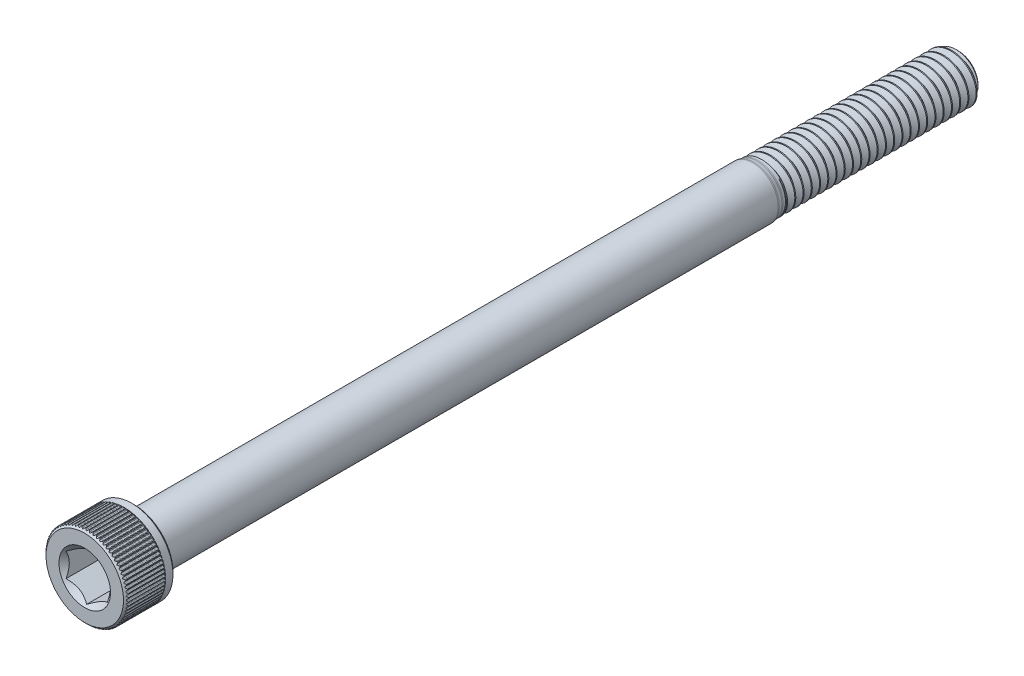
SolidWorks part; units mm, degrees
ref_plane "Front Plane" through (0, 0, 0) normal (0, 0, 1) x (1, 0, 0)
ref_plane "Top Plane" through (0, 0, 0) normal (0, 1, 0) x (1, 0, 0)
ref_plane "Right Plane" through (0, 0, 0) normal (1, 0, 0) x (0, 0, -1)
sketch "Sketch1" plane through (0, 0, 0) normal (1, 0, 0) x (0, 0, -1)
  line L0 (-53, 0) -> (53, 0) construction
  line L1 (53, 0) -> (53, 2.3505) construction
  line L2 (53, 2.3505) -> (52.3505, 3) construction
  line L3 (52.3505, 3) -> (52.25, 3) construction
  line L4 (52.25, 3) -> (-47, 3) construction
  line L5 (-47, 3) -> (-47, 5) construction
  line L6 (-47, 5) -> (-53, 5) construction
  line L7 (-53, 5) -> (-53, 0) construction
  line L8 (53, 2.3505) -> (53, 3) construction
  line L9 (52.9375, 3.1083) -> (53.4375, 2.2422) construction
  line L10 (53.4375, 2.2422) -> (53.9375, 3.1083) construction
  line L11 (53.9375, 3.1083) -> (52.9375, 3.1083) construction
  line L12 (53.4375, 3.1083) -> (53.4375, 3) construction
  line L13 (53.4375, 2.2422) -> (53.4375, 2.3505) construction
  line L14 (53.375, 2.3505) -> (53.5, 2.3505) construction
  line L15 (53, 3) -> (53.875, 3) construction
  line L16 (52.9688, 3.0541) -> (53.9062, 3.0541) construction
  line L17 (53, 0) -> (53, -3) construction
  line L18 (-47.3, 5) -> (-47, 4.7) construction
  line L19 (-52.7, 5) -> (-53, 4.7) construction
  line L20 (-47, 3) -> (-47, 0) construction
  line L21 (-47, 1.5) -> (-13.6667, 1.5) construction
  line L22 (-13.6667, 1.5) -> (19.6667, 1.5) construction
  line L23 (19.6667, 1.5) -> (53, 1.5) construction
  line L24 (-13.6667, 1.5) -> (-13.6667, 3) construction
  line L25 (-13.6667, 3) -> (-13.6667, 5) construction
  line L26 (19.6667, 1.5) -> (19.6667, 5) construction
  point P0 (-53, 2.5)
  point P3 (50.5, 3)
  point P4 (0, 0)
  point P18 (19.6667, 3)
  point P22 (53.4375, 2.3505)
  point P24 (52.25, 3)
  point P25 (53.4375, 3)
  point P28 (53.4375, 3.0541)
  point P29 (50.5, -3)
  point P30 (-13.6667, 3)
  point P31 (-50, 5)
  point P37 (-48.05, 5)
  point P38 (-52.55, 5)
  point P45 (-13.6667, 1.5)
  point P46 (19.6667, 1.5)
  point P49 (29, 3)
  dimension "D1" = 45
  dimension "D2" = 0.125
  dimension "D7" = 0.3
  dimension "D8" = 0.3
  dimension "D9" = 0.3
  dimension "D10" = 0.15
  dimension "D11" = 0.75
  dimension "Drive Size" = 5
  dimension "Head Diameter" = 10
  dimension "Head Height" = 6
  dimension "Thread Pitch" = 1
  dimension "Thread Size" = 6
  dimension "Length" = 100
  dimension "D12" = 0.75
  dimension "D4" = 2.5
  dimension "Minimum Thread Length" = 24
  dimension "D3" = 76
sketch "Sketch2" plane through (0, 0, 0) normal (1, 0, 0) x (0, 0, -1)
  line L0 (-53, 0) -> (-53, 4.7)
  line L1 (-52.7, 5) -> (-47.3, 5)
  line L2 (-47, 4.7) -> (-47, 3.4083)
  line L4 (52.3505, 3) -> (53, 2.3505)
  line L5 (53, 2.3505) -> (53, 0)
  line L6 (-47, 5) -> (-53, 5) construction
  line L7 (53, 0) -> (-53, 0)
  line L8 (-52.7, 5) -> (-53, 4.7) construction
  line L10 (-52.7, 5) -> (-53, 4.7)
  line L14 (-47.3, 5) -> (-47, 4.7) construction
  line L16 (-47.3, 5) -> (-47, 4.7)
  line L17 (-47, 3) -> (-47, 5) construction
  line L18 (-46.7, 3.1083) -> (28.0069, 3.1083)
  line L19 (28.6989, 3) -> (52.3505, 3)
  line L20 (52.25, 3) -> (-47, 3) construction
  line L21 (28.1532, 3.0938) -> (28.5526, 3.0144)
  line L22 (53.9375, 3.1083) -> (52.9375, 3.1083) construction
  arc A1 (-47, 3.4083) -> (-46.7, 3.1083) centre (-46.7, 3.4083) ccw
  arc A2 (28.0069, 3.1083) -> (28.1532, 3.0938) centre (28.0069, 2.3583) cw
  arc A3 (28.5526, 3.0144) -> (28.6989, 3) centre (28.6989, 3.75) ccw
  point P39 (28.625, 3)
  dimension "D3" = 0.3
  dimension "D6" = 0.75
  dimension "D4" = 11.25
  dimension "D5" = 0.375
revolve "Revolve1" add sketch "Sketch2" angle 360 about L7
sketch "Sketch3" plane through (0, 0, 53) normal (0, 0, 1) x (1, 0, 0)
  line L1 (2.5, -1.4434) -> (2.5, 1.4434)
  line L2 (2.5, 1.4434) -> (0, 2.8868)
  line L3 (0, 2.8868) -> (-2.5, 1.4434)
  line L4 (-2.5, 1.4434) -> (-2.5, -1.4434)
  line L5 (-2.5, -1.4434) -> (0, -2.8868)
  line L6 (0, -2.8868) -> (2.5, -1.4434)
  circle A0 centre (0, 0) radius 2.5 construction
  circle A1 centre (0, 0) radius 5 construction
  circle A2 centre (0, 0) radius 5 construction
  circle A3 centre (0, 0) radius 2.8868 construction
extrude "Cut-Extrude1" cut sketch "Sketch3" against normal offset from surface (5 mm away) 1 up to face at (0, 4.7, 47)
sketch "Sketch4" plane through (0, 0, 53) normal (0, 0, 1) x (1, 0, 0)
  circle A0 centre (0, 0) radius 3.125
  dimension "D1" = 6.25
extrude "Cut-Extrude2" cut sketch "Sketch4" against normal up to vertex (3 mm away) draft 45 up to point (0, 5, 50)
sketch "Sketch11" plane through (0, 0, 0) normal (1, 0, 0) x (0, 0, -1)
  line L0 (-53, 0) -> (53, 0) construction
  line L1 (-53, 0) -> (53, 0) construction
  line L2 (-40.35, 0) -> (-40.35, 3) construction
  line L3 (52.25, 3) -> (-47, 3) construction
  line L4 (21.3569, 0) -> (21.3569, 3) construction
  point P2 (-40.35, 0)
  point P3 (21.3569, 0)
  dimension "D1" = 6.65
  dimension "D2" = 6.65
sketch "Sketch6" plane through (0, 0, -53) normal (0, 0, -1) x (-1, 0, 0)
  circle A0 centre (0, 0) radius 3
curve "Helix/Spiral1" pitch 1 height 25 radius 3 centre (0, 0, -53) axis (0, 0, 1) start towards (0, 1, 0)
sketch "Sketch10" plane through (0, 0, 0) normal (1, 0, 0) x (0, 0, -1)
  line L0 (29, -3) -> (29, 3)
  line L2 (-53, 0) -> (53, 0) construction
  point P3 (29, 0)
split "Split1" trim tools "Sketch10" bodies to split 106 resulting bodies 114 115
sketch "Sketch7" plane through (0, 0, 0) normal (1, 0, 0) x (0, 0, -1)
  line L0 (52.9688, 3.0541) -> (53.9062, 3.0541)
  line L1 (53.9062, 3.0541) -> (53.5, 2.3505)
  line L2 (53.5, 2.3505) -> (53.375, 2.3505)
  line L3 (53.375, 2.3505) -> (52.9688, 3.0541)
sweep "Cut-Sweep1" cut profiles "Sketch7" path "Helix/Spiral1" align with end faces yes
sketch "Sketch8" plane through (0, 0, 0) normal (1, 0, 0) x (0, 0, -1)
  line L0 (-47, 0) -> (-47, 3)
  line L2 (-47, 3) -> (29, 3)
  line L4 (29, 3) -> (30.7321, 0)
  line L5 (30.7321, 0) -> (-47, 0)
  line L6 (52.25, 3) -> (-47, 3) construction
  line L7 (-53, 0) -> (53, 0) construction
  dimension "D1" = 60
  dimension "D2" = 24
revolve "Revolve2" add sketch "Sketch8" angle 360 about L5
ref_plane "Plane1" through (0, 0, 53) normal (0, 0, 1) x (1, 0, 0)
sketch "Sketch12" plane through (0, 0, 53) normal (0, 0, 1) x (1, 0, 0)
  line L0 (0, 0) -> (0.1745, 4.997) construction
  line L1 (0, 0) -> (-0.1745, 4.997) construction
  line L2 (0, 5.125) -> (0, 4.875) construction
  line L3 (-0.3025, 5.125) -> (-0.0897, 4.9122)
  line L4 (0.0897, 4.9122) -> (0.3025, 5.125)
  line L5 (0.3025, 5.125) -> (-0.3025, 5.125)
  circle A0 centre (0, 0) radius 5 construction
  arc A1 (-0.0897, 4.9122) -> (0.0897, 4.9122) centre (0, 5.0019) ccw
  point P12 (0, 5)
  point P14 (0, 5.125)
  dimension "D2" = 0.125
  dimension "D1" = 4
extrude "Cut-Extrude3" cut sketch "Sketch12" against normal blind 4.8
pattern_circular "CirPattern1" count 72 over 360 about axis through (0, 0, 53) along (0, 0, -1) of "Cut-Extrude3"
equation "\"D2@Sketch1\" = \"Thread Pitch@Sketch1\" / 8"
equation "\"D4@Helix/Spiral1\" = \"Thread Pitch@Sketch1\""
equation "\"D7@Sketch1\" = \"Head Height@Sketch1\" * .05"
equation "\"D8@Sketch1\"=\"D7@Sketch1\""
equation "\"D9@Sketch1\"=\"D7@Sketch1\""
equation "\"D10@Sketch1\"=\"D7@Sketch1\"/2"
equation "\"D11@Sketch1\"=\"D10@Sketch1\"*5"
equation "\"D4@Sketch1\"=\"Thread Pitch@Sketch1\"*2.5"
equation "\"D12@Sketch1\"=\"Thread Pitch@Sketch1\"*.75"
equation "\"D3@Helix/Spiral1\"=\"Minimum Thread Length@Sketch1\"+\"Thread Pitch@Sketch1\""
equation "\"D2@Sketch8\"=\"Minimum Thread Length@Sketch1\""
equation "\"D3@Sketch2\"=\"Thread Size@Sketch1\"*0.05"
equation "\"D5@Sketch2\"=\"D12@Sketch1\"*0.5"
equation "\"D6@Sketch2\"=\"Thread Size@Sketch1\"*0.125"
equation "\"D1@Sketch11\"=(\"Length@Sketch1\"-\"Minimum Thread Length@Sketch1\")*0.0875"
equation "\"D2@Sketch11\"=\"D1@Sketch11\""
equation "\"D1@Sketch4\"=\"Drive Size@Sketch1\"*1.25"
equation "\"D2@Sketch12\"=\"Head Diameter@Sketch1\"*.0125"
equation "\"D1@Cut-Extrude3\"=\"Head Height@Sketch1\"*.8"
equation "\"D1@CirPattern1\"=\"D3@CirPattern1\"/(1.25*\"D1@Sketch12\")"
